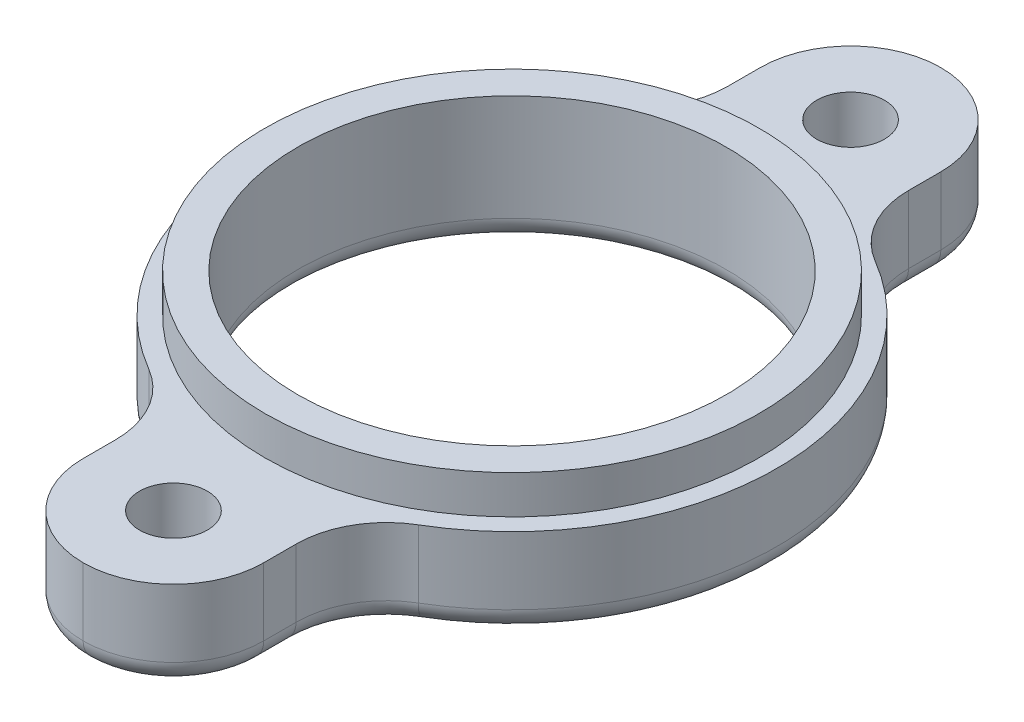
SolidWorks part; units mm, degrees
ref_plane "Piano frontale" through (0, 0, 0) normal (0, 0, 1) x (1, 0, 0)
ref_plane "Piano superiore" through (0, 0, 0) normal (0, 1, 0) x (1, 0, 0)
ref_plane "Piano destro" through (0, 0, 0) normal (1, 0, 0) x (0, 0, -1)
sketch "Schizzo1" plane through (0, 0, 0) normal (0, 1, 0) x (1, 0, 0)
  circle A0 centre (0, 0) radius 10.95
  circle A1 centre (0, 0) radius 9.5
  dimension "D1" = 21.9
  dimension "D2" = 19
extrude "Estrusione-Estrusione1" add sketch "Schizzo1" along normal blind 1.7
sketch "Schizzo2" plane through (0, 0, 0) normal (0, 1, 0) x (1, 0, 0)
  line L1 (-4, -19) -> (4, -19)
  line L2 (-4, -19) -> (-4, 19)
  line L3 (-4, 19) -> (4, 19)
  line L4 (4, -19) -> (4, 19)
  circle A0 centre (0, 0) radius 9.5
  circle A1 centre (0, 0) radius 11.75
  circle A2 centre (0, 0) radius 9.5 construction
  circle A3 centre (0, 0) radius 15 construction
  circle A4 centre (0, 15) radius 1.5
  circle A5 centre (0, -15) radius 1.5
  point P16 (0, 19)
  dimension "D1" = 23.5
  dimension "D2" = 30
  dimension "D3" = 3
  dimension "D4" = 3
  dimension "D5" = 8
  dimension "D6" = 4
  dimension "D7" = 4
extrude "Estrusione-Estrusione2" add sketch "Schizzo2" against normal blind 4 contours A1 L4 L3 L2 A4 | A1 L2 L1 L4 A5 | L2 A1 A0 | L4 A1 A0 | L4 A1 L2 A0 | L2 A1 L4 A0 region at (-3.8872, 0, 15.0241) region at (-11.5158, 0, 0) region at (0, 0, 10.3597) region at (4.2342, 0, 9.8325) region at (0, 0, -10.3597) region at (-3.8872, 0, -15.0241)
fillet "Raccordo1" radius 4 8 edges at (4, -2, -11.0482) (-4, -2, -19) (-4, -2, -11.0482) (-4, -2, 11.0482) (4, -2, 11.0482) (4, -2, 19) (-4, -2, 19) (4, -2, -19)
fillet "Raccordo2" radius 1 15 edges at (4.5267, -4, 11.5829) (4, -4, 14.2835) (2.8284, -4, 17.8284) (-2.8284, -4, 17.8284) (-4, -4, 14.2835) (-4.5267, -4, 11.5829) (-11.75, -4, 0) (-4.5267, -4, -11.5829) (-4, -4, -14.2835) (-2.8284, -4, -17.8284) (2.8284, -4, -17.8284) (4, -4, -14.2835) (4.5267, -4, -11.5829) (0, -4, 9.5) (11.75, -4, 0)
